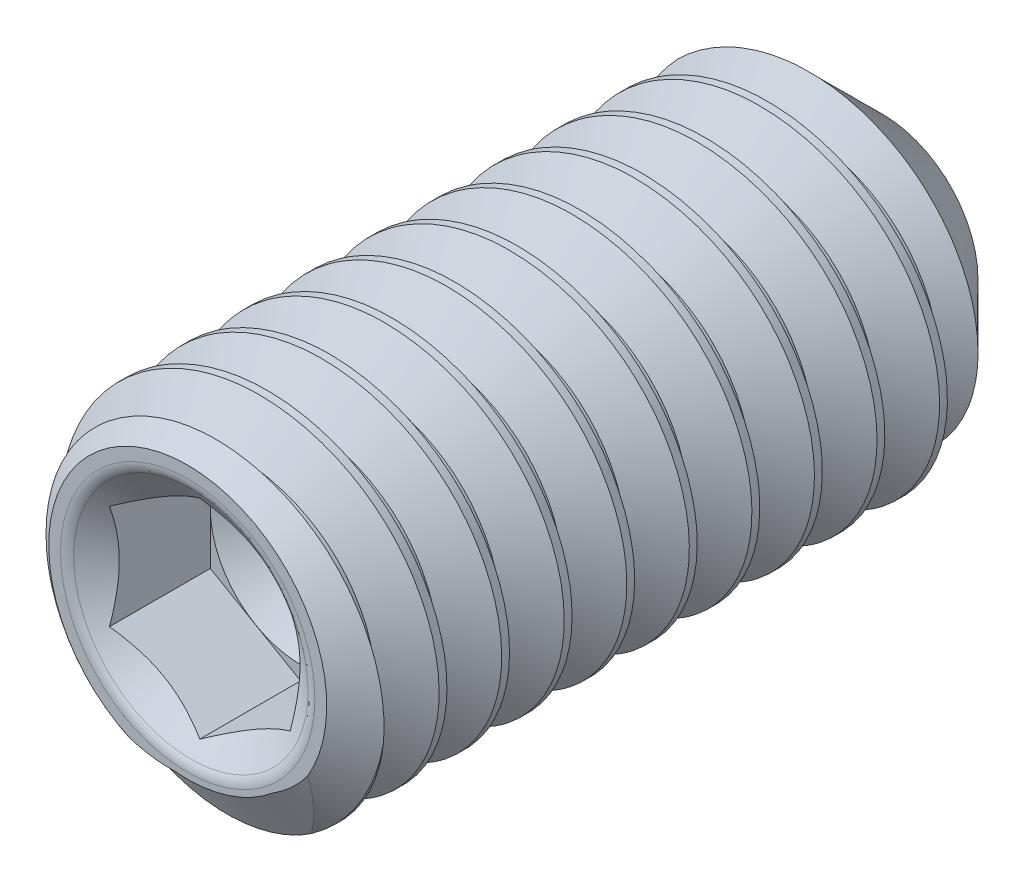
SolidWorks part; units mm, degrees
ref_plane "Front" through (0, 0, 0) normal (0, 0, 1) x (1, 0, 0)
ref_plane "Top" through (0, 0, 0) normal (0, 1, 0) x (1, 0, 0)
ref_plane "Right" through (0, 0, 0) normal (1, 0, 0) x (0, 0, -1)
sketch "Sketch22" plane through (0, 0, 0) normal (1, 0, 0) x (0, 0, -1)
  line L0 (-2.2942, 0) -> (-2.2942, 1)
  line L1 (-2.2942, 1) -> (-2.1192, 1.25)
  line L2 (-2.1192, 1.25) -> (2.1407, 1.25)
  line L3 (2.1407, 1.25) -> (2.7058, 0.685)
  line L4 (2.7058, 0.685) -> (2.2942, 0)
  line L5 (2.2942, 0) -> (-2.2942, 0)
  line L6 (2.2942, 0) -> (2.7058, 0) construction
  line L7 (2.7058, 0) -> (2.7058, 0.685) construction
  line L8 (2.7058, -0.685) -> (2.2942, 0) construction
  line L9 (-2.1192, -1.25) -> (2.1407, -1.25) construction
  dimension "Dia" = 2.5
  dimension "Length" = 5
  dimension "D3" = 35
  dimension "D5" = 118
  dimension "D6" = 45
  dimension "D7" = 2
revolve "Revolve1" add sketch "Sketch22" angle 360 about L6
ref_plane "Plane1" through (0, 0, -2.7058) normal (0, 0, 1) x (1, 0, 0)
sketch "Sketch27" plane through (0, 0, -2.7058) normal (0, 0, 1) x (1, 0, 0)
  circle A0 centre (0, 0) radius 1.25 construction
  circle A1 centre (0, 0) radius 1.25
curve "Helix/Spiral1" pitch 0.45 height 5.45 radius 1.25 centre (0, 0, -2.7058) axis (0, 0, 1) start towards (0, 1, 0)
sketch "Sketch28" plane through (0, 0, 0) normal (1, 0, 0) x (0, 0, -1)
  line L0 (2.7058, 1.25) -> (3.0995, 1.25)
  line L1 (3.0995, 1.25) -> (2.9308, 0.9577)
  line L2 (2.9308, 0.9577) -> (2.8745, 0.9577)
  line L3 (2.8745, 0.9577) -> (2.7058, 1.25)
  line L4 (2.7902, 1.1039) -> (3.0152, 1.1039) construction
  line L6 (-2.1192, 1.25) -> (2.1407, 1.25) construction
  dimension "D1" = 0.0563
  dimension "D3" = 60
  dimension "D2" = 0.225
sweep "Cut-Sweep2" cut profiles "Sketch28" path "Helix/Spiral1" align with end faces yes
sketch "Sketch23" plane through (0, 0, 2.2942) normal (0, 0, 1) x (1, 0, 0)
  line L1 (0, 0.7506) -> (-0.65, 0.3753)
  line L2 (-0.65, 0.3753) -> (-0.65, -0.3753)
  line L3 (-0.65, -0.3753) -> (0, -0.7506)
  line L4 (0, -0.7506) -> (0.65, -0.3753)
  line L5 (0.65, -0.3753) -> (0.65, 0.3753)
  line L6 (0.65, 0.3753) -> (0, 0.7506)
  circle A0 centre (0, 0) radius 0.65 construction
  dimension "Hex" = 1.3
extrude "Cut-Extrude10" cut sketch "Sketch23" against normal blind 0.8125
sketch "Sketch24" plane through (0, 0, 2.2942) normal (0, 0, 1) x (1, 0, 0)
  line L0 (0, 0.7506) -> (0, 1) construction
  circle A0 centre (0, 0) radius 0.8753
  point P5 (0, 0.8753)
  dimension "D1" = 0.1247
extrude "Cut-Extrude11" cut sketch "Sketch24" against normal through all draft 55
sketch "Sketch26" plane through (0, 0, 1.4817) normal (0, 0, 1) x (1, 0, 0)
  circle A0 centre (0, 0) radius 0.65 construction
  circle A1 centre (0, 0) radius 0.65
extrude "Cut-Extrude12" cut sketch "Sketch26" against normal through all draft 60
sketch "Sketch30" plane through (0, 0, 0) normal (1, 0, 0) x (0, 0, -1)
  line L0 (-2.1192, 1.25) -> (2.1407, 1.25) construction
  line L1 (-2.2942, 0) -> (-2.2942, 1) construction
  line L2 (2.7058, 0) -> (2.7058, 0.685) construction
  line L3 (-2.1192, -1.25) -> (2.1407, -1.25) construction
  point P0 (-2.2942, 1.25)
  point P1 (2.7058, 1.25)
  point P2 (2.7058, -1.25)
  point P11 (1.5808, -1.25)
  dimension "D1" = 1.125
sketch "Sketch31" plane through (0, 0, 0) normal (1, 0, 0) x (0, 0, -1)
  line L2 (2.2942, 0) -> (2.7058, -0.685)
  line L3 (2.7058, 0.685) -> (2.2942, 0)
fillet "Fillet2" radius 0.1247 1 edges at (0.8753, 0, 2.2942)
equation "\"D7@Sketch22\"=\"Dia@Sketch22\"*.8"
equation "\"D1@Sketch28\" = \"D4@Helix/Spiral1\" * .125"
equation "\"D2@Sketch28\" = \"D4@Helix/Spiral1\" * .5"
equation "\"D3@Helix/Spiral1\" = \"Length@Sketch22\" + \"D4@Helix/Spiral1\""
equation "\"D1@Sketch30\" = \"D4@Helix/Spiral1\" * 2.5"
equation "\"hex Depth@Cut-Extrude10\" = \"Hex@Sketch23\" * .625"
equation "\"D1@Fillet2\" = \"D1@Sketch24\""
